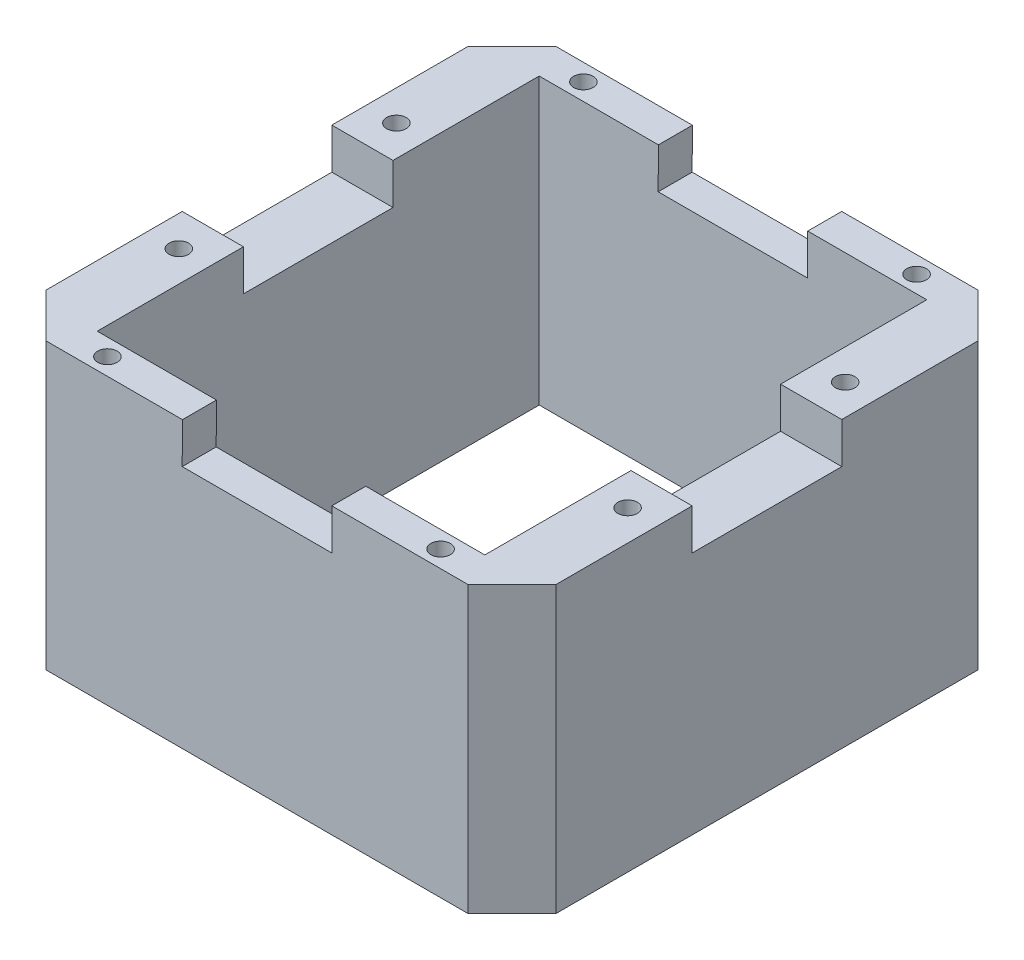
SolidWorks part; units mm, degrees
material "Copper"
ref_plane "Front Plane" through (0, 0, 0) normal (0, 0, 1) x (1, 0, 0)
ref_plane "Top Plane" through (0, 0, 0) normal (0, 1, 0) x (1, 0, 0)
ref_plane "Right Plane" through (0, 0, 0) normal (1, 0, 0) x (0, 0, -1)
sketch "Sketch2" plane through (0, 0, 0) normal (0, 1, 0) x (1, 0, 0)
  line L0 (-43.315, 19.4626) -> (-43.315, -55.5374)
  line L1 (-34.315, 14.4626) -> (22.685, 14.4626)
  line L2 (-34.315, 14.4626) -> (-34.315, -50.5374)
  line L3 (-34.315, -50.5374) -> (22.685, -50.5374)
  line L4 (22.685, 14.4626) -> (22.685, -50.5374)
  line L5 (-43.315, -55.5374) -> (31.685, -55.5374)
  line L6 (31.685, 19.4626) -> (31.685, -55.5374)
  line L7 (-43.315, 19.4626) -> (31.685, 19.4626)
  line L8 (-43.315, -18.0374) -> (-34.315, -18.0374) construction
  line L9 (22.685, -18.0374) -> (31.685, -18.0374) construction
  line L10 (-5.815, 19.4626) -> (-5.815, 14.4626) construction
  line L11 (-5.815, 14.4626) -> (-5.815, -50.5374) construction
  line L12 (-5.815, -50.5374) -> (-5.815, -55.5374) construction
  dimension "D1" = 57
  dimension "D2" = 65
  dimension "D3" = 9
  dimension "D4" = 5
  dimension "D7" = 75
extrude "Boss-Extrude1" add sketch "Sketch2" along normal blind 41.91
sketch "Sketch4" plane through (0, 0, -19.4626) normal (0, 0, -1) x (-1, 0, 0)
  line L3 (16.7827, 41.915) -> (-5.1804, 41.91)
  line L4 (-31.685, 41.91) -> (43.315, 41.91) construction
  line L5 (-5.1804, 41.91) -> (-5.1804, 35.91)
  line L6 (-5.1804, 35.91) -> (16.8196, 35.91)
  line L7 (16.7827, 41.915) -> (16.8196, 35.91)
  point P3 (5.8103, 41.91)
  point P12 (5.8011, 41.9125)
  point P13 (5.8196, 35.91)
  dimension "D1" = 6
  dimension "D2" = 22
extrude "Cut-Extrude1" cut sketch "Sketch4" against normal blind 92.91
sketch "Sketch6" plane through (-43.315, 0, 0) normal (-1, 0, 0) x (0, 0, 1)
  line L0 (18.0374, 41.91) -> (18.0374, 0) construction
  line L1 (-19.4626, 41.91) -> (55.5374, 41.91) construction
  line L2 (-19.4626, 0) -> (55.5374, 0) construction
  line L3 (29.0374, 41.91) -> (7.0374, 41.91)
  line L4 (7.0374, 41.91) -> (7.0374, 35.91)
  line L5 (7.0374, 35.91) -> (29.0374, 35.91)
  line L6 (29.0374, 41.91) -> (29.0374, 35.91)
  point P10 (18.0374, 35.91)
  dimension "D1" = 6
  dimension "D2" = 11
extrude "Cut-Extrude2" cut sketch "Sketch6" against normal blind 92.91
sketch "Sketch7" plane through (0, 41.91, 0) normal (0, 1, 0) x (1, 0, 0)
  line L0 (31.685, 12.9968) -> (25.2192, 19.4626)
  line L1 (25.2192, 19.4626) -> (31.685, 19.4626)
  line L2 (31.685, -7.0374) -> (31.685, 19.4626) construction
  line L3 (31.685, 19.4626) -> (5.1804, 19.4626) construction
  line L4 (31.685, 19.4626) -> (31.685, 12.9968)
  dimension "D1" = 9.144
extrude "Cut-Extrude3" cut sketch "Sketch7" against normal blind 92.91
sketch "Sketch11" plane through (0, 41.91, 0) normal (0, 1, 0) x (1, 0, 0)
  circle A0 centre (-5.815, -18.0374) radius 53.033
sketch "Sketch13" plane through (0, 41.91, 0) normal (0, 1, 0) x (1, 0, 0)
  line L0 (-34.315, 14.4626) -> (-5.815, -18.0374)
  line L1 (-5.815, -18.0374) -> (22.685, 14.4626)
  line L2 (22.685, -50.5374) -> (-5.815, -18.0374)
  line L3 (-34.315, -50.5374) -> (-5.815, -18.0374)
ref_axis "Axis1" through (-5.815, 41.91, 18.0374) along (0, 1, 0)
pattern_circular "CirPattern1" count 4 over 360 about axis through (-5.815, 41.91, 18.0374) along (0, 1, 0) of "Cut-Extrude3"
hole_wizard "Tap Drill for #6-40 Tap1" positions "Sketch19" profile "Sketch18" hole size "#6-40" standard "ANSI Inch"
sketch "Sketch19" plane through (0, 41.91, 0) normal (0, 1, 0) x (1, 0, 0)
  line L0 (-5.8196, 19.4626) -> (-5.8196, -55.5374)
  line L1 (5.1804, 19.4626) -> (-16.8196, 19.4626) construction
  line L2 (5.1804, -55.5374) -> (-16.8196, -55.5374) construction
  line L6 (-38.815, -2.0374) -> (-34.315, -2.0374)
  line L7 (-34.315, 14.4626) -> (-34.315, -7.0374) construction
  line L9 (-38.815, -2.0374) -> (-43.315, -2.0374)
  line L10 (-43.315, 12.9968) -> (-43.315, -7.0374) construction
  line L12 (-38.815, -34.0374) -> (-34.315, -34.0374)
  line L13 (-34.315, -29.0374) -> (-34.315, -50.5374) construction
  line L15 (-38.815, -34.0374) -> (-43.315, -34.0374)
  line L16 (-43.315, -29.0374) -> (-43.315, -49.0716) construction
  line L17 (-34.315, -7.0374) -> (-43.315, -7.0374) construction
  line L18 (-34.315, -29.0374) -> (-43.315, -29.0374) construction
  point P0 (-38.815, -2.0374)
  point P4 (-38.815, -34.0374)
  dimension "D1" = 5
  dimension "D2" = 5
sketch "Sketch18" plane through (-38.815, 41.91, 2.0374) normal (1, 0, 0) x (0, 0, 1)
  line L0 (0, 0) -> (0, 20.8623)
  line L1 (0, 20.8623) -> (1.4351, 20)
  line L2 (1.4351, 20) -> (1.4351, 0)
  line L5 (1.4351, 0) -> (0, 0)
  line L10 (0, 20.8623) -> (-1.4351, 20) construction
  line L11 (0, -6.35) -> (0, 107.95) construction
  dimension "Hole Dia." = 2.8702
  dimension "Hole Depth" = 20
  dimension "Drill Angle" = 118
pattern_circular "CirPattern2" count 2 over 360 about axis through (-5.815, 41.91, 18.0374) along (0, 1, 0) of "Tap Drill for #6-40 Tap1"
hole_wizard "Tap Drill for #6-40 Tap2" positions "Sketch22" profile "Sketch23" hole size "#6-40" standard "ANSI Inch"
sketch "Sketch22" plane through (0, 41.91, 0) normal (0, 1, 0) x (1, 0, 0)
  line L0 (-30.315, 16.9626) -> (-30.315, 19.4626)
  line L1 (-16.7828, 19.4626) -> (-36.8492, 19.4626) construction
  line L3 (-30.315, 16.9626) -> (-30.315, 14.4626)
  line L4 (-16.7828, 14.4626) -> (-34.315, 14.4626) construction
  line L7 (-43.315, 12.9968) -> (-43.315, -7.0374) construction
  line L8 (31.685, -7.0374) -> (31.685, 12.9968) construction
  line L9 (-30.315, 16.9626) -> (18.685, 16.9626)
  point P0 (-30.315, 16.9626)
  point P20 (18.685, 16.9626)
  dimension "D1" = 13
  dimension "D2" = 13
sketch "Sketch23" plane through (-30.315, 41.91, -16.9626) normal (1, 0, 0) x (0, 0, 1)
  line L0 (0, 0) -> (0, 20.8623)
  line L1 (0, 20.8623) -> (1.4351, 20)
  line L2 (1.4351, 20) -> (1.4351, 0)
  line L5 (1.4351, 0) -> (0, 0)
  line L10 (0, 20.8623) -> (-1.4351, 20) construction
  line L11 (0, -6.35) -> (0, 107.95) construction
  dimension "Hole Dia." = 2.8702
  dimension "Hole Depth" = 20
  dimension "Drill Angle" = 118
sketch "Sketch25" plane through (0, 35.91, 0) normal (0, 1, 0) x (1, 0, 0)
pattern_circular "CirPattern4" count 2 over 360 about axis through (-5.815, 41.91, 18.0374) along (0, 1, 0) of "Tap Drill for #6-40 Tap2"
